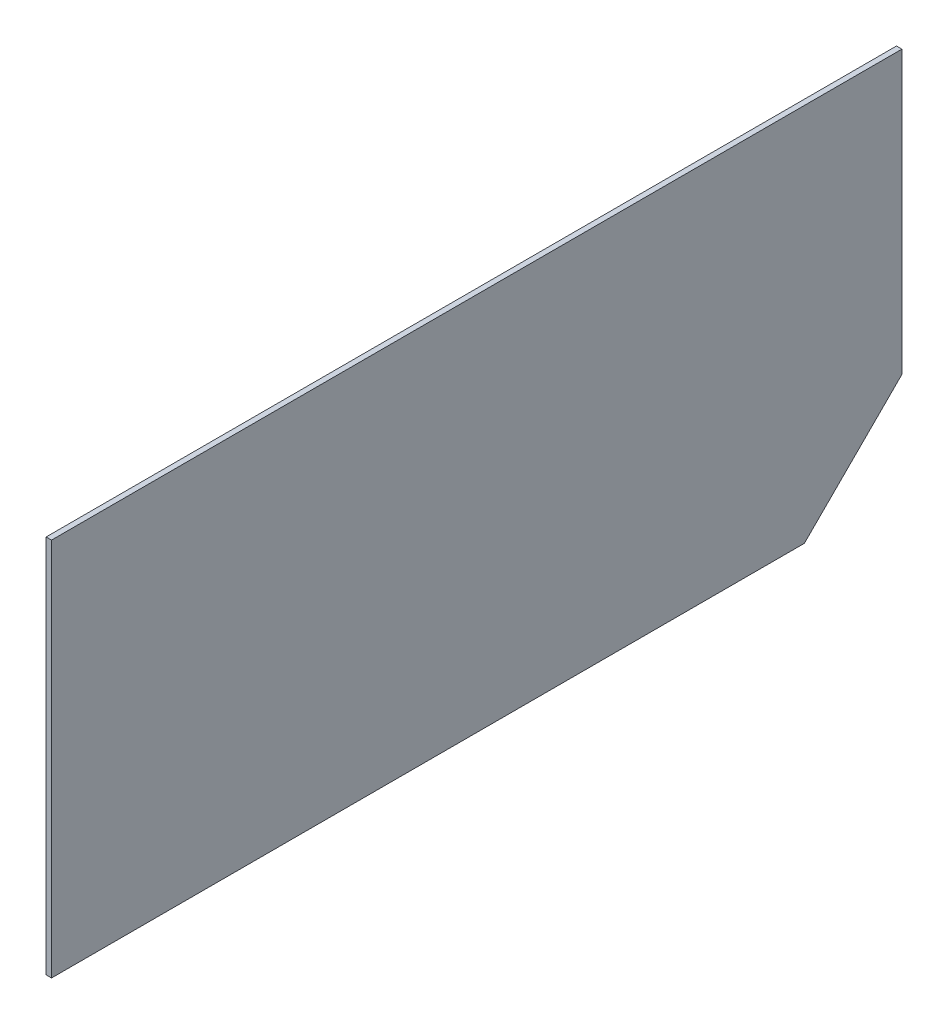
SolidWorks part; units mm, degrees
material "6061-T6 (SS)"
ref_plane "X-Y Datum" through (0, 0, 0) normal (0, 0, 1) x (1, 0, 0)
ref_plane "X-Z Datum" through (0, 0, 0) normal (0, 1, 0) x (1, 0, 0)
ref_plane "Y-Z Datum" through (0, 0, 0) normal (1, 0, 0) x (0, 0, -1)
sketch "Sketch1" plane through (0, 0, 0) normal (1, 0, 0) x (0, 0, -1)
  line L1 (-249.174, 82.55) -> (249.174, 82.55)
  line L2 (-249.174, 82.55) -> (-249.174, -82.55)
  line L3 (-249.174, -82.55) -> (249.174, -82.55)
  line L4 (249.174, 82.55) -> (249.174, -82.55)
  line L5 (-249.174, 82.55) -> (249.174, -82.55) construction
  line L6 (-249.174, -82.55) -> (249.174, 82.55) construction
  point P0 (0, 0)
  dimension "D1" = 165.1
  dimension "D2" = 498.348
extrude "Boss-Extrude1" add sketch "Sketch1" along normal mid plane 3.175
sketch "Sketch2" plane through (1.5875, 0, 0) normal (1, 0, 0) x (0, 0, -1)
  line L3 (192.024, -139.7) -> (-249.174, -139.7)
  line L5 (-249.174, -82.55) -> (249.174, -82.55) construction
  line L6 (-249.174, -82.55) -> (249.174, -82.55)
  line L7 (-249.174, -82.55) -> (-249.174, -139.7)
  line L12 (192.024, -139.7) -> (249.174, -82.55)
  point P1 (248.4459, -89.6281)
  point P2 (185.8407, -136.525)
  point P5 (202.9668, -105.6842)
  point P6 (249.174, -88.9)
  point P10 (249.174, -82.55)
  point P15 (0, 0)
  point P16 (261.874, -82.55)
  line M10 (-249.174, -82.55) -> (249.174, -82.55)
  dimension "D1" = 45
  dimension "D5" = 57.15
extrude "Boss-Extrude2" add sketch "Sketch2" against normal blind 3.175 contours L3 L12 M10 region at (1.5875, -110.5456, 13.9978)
